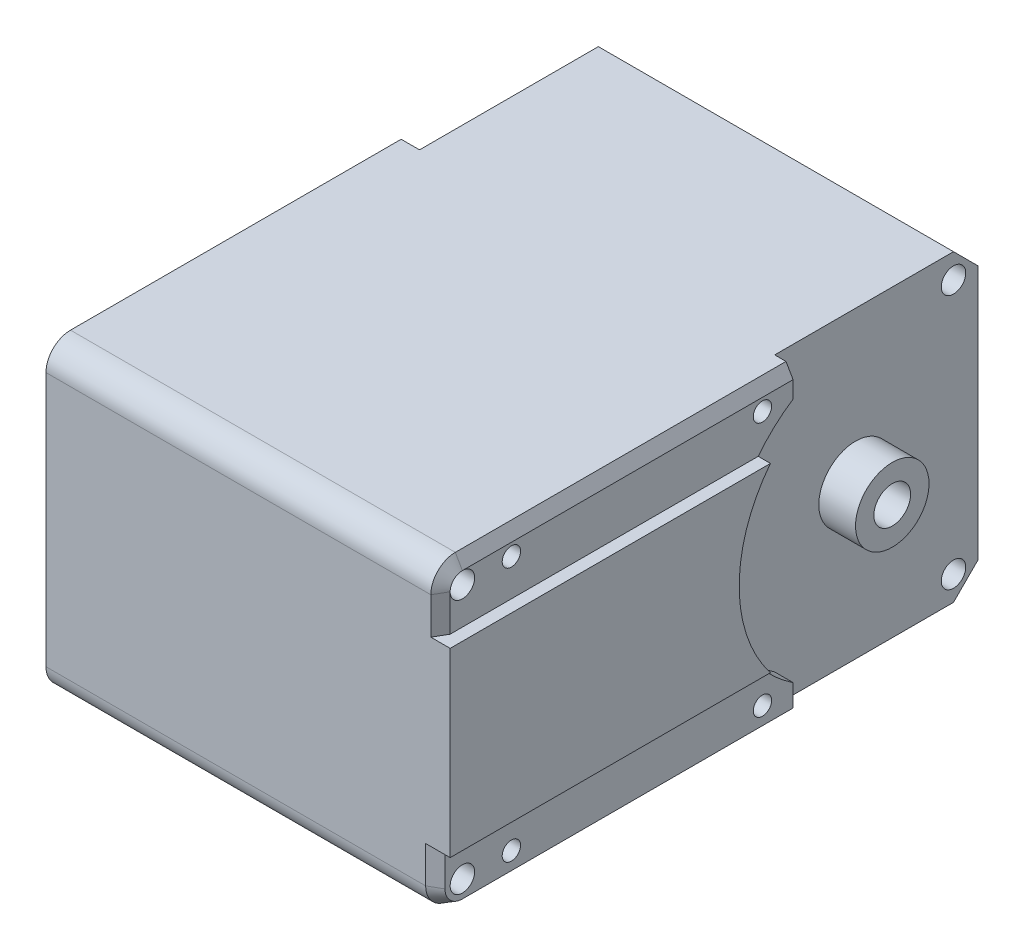
SolidWorks part; units mm, degrees
other "Markup1"
sketch "Sketch5" plane through (27.3, 11.5, -22.8) normal (0.9422, 0.1493, -0.3) x (0.1093, -0.9832, -0.146)
ref_plane "Front Plane" through (0, 0, 0) normal (0, 0, 1) x (1, 0, 0)
ref_plane "Top Plane" through (0, 0, 0) normal (0, 1, 0) x (1, 0, 0)
ref_plane "Right Plane" through (0, 0, 0) normal (1, 0, 0) x (0, 0, -1)
sketch "Sketch3" plane through (0, 0, 0) normal (1, 0, 0) x (0, 0, -1)
  line L1 (-22.8, -12.4) -> (22.8, -12.4)
  line L2 (-22.8, -12.4) -> (-22.8, 12.4)
  line L3 (-22.8, 12.4) -> (22.8, 12.4)
  line L4 (22.8, -12.4) -> (22.8, 12.4)
  line L5 (-22.8, -12.4) -> (22.8, 12.4) construction
  line L6 (-22.8, 12.4) -> (22.8, -12.4) construction
  point P0 (0, 0)
  dimension "D1" = 24.8
  dimension "D2" = 45.6
extrude "Boss-Extrude1" add sketch "Sketch3" along normal blind 29
sketch "Sketch4" plane through (29, 0, 0) normal (1, 0, 0) x (0, 0, -1)
  line L0 (-22.8, -12.4) -> (22.8, -12.4) construction
  line L1 (-22.8, 12.4) -> (6.2, 12.4)
  line L2 (-22.8, 12.4) -> (-22.8, -12.4)
  line L3 (-22.8, -12.4) -> (6.2, -12.4)
  line L4 (6.2, 12.4) -> (6.2, -12.4)
  line L5 (22.8, 0) -> (12.8, 0) construction
  line L6 (22.8, -12.4) -> (22.8, 12.4) construction
  circle A0 centre (12.8, 0) radius 14.5
  dimension "D3" = 29
  dimension "D1" = 29
  dimension "D2" = 10
extrude "Boss-Extrude2" add sketch "Sketch4" along normal blind 1.5 contours L2 L1 L4 L3
sketch "Sketch6" plane through (29, 0, 0) normal (1, 0, 0) x (0, 0, -1)
  line L0 (22.8, 0) -> (12.8, 0) construction
  line L1 (22.8, -12.4) -> (22.8, 12.4) construction
  circle A0 centre (12.8, 0) radius 12
  dimension "D1" = 10
extrude "Cut-Extrude1" cut sketch "Sketch6" along normal up to surface (1.5 mm away) up to face at (30.5, 0, 8.3)
sketch "Sketch7" plane through (30.5, 0, 0) normal (1, 0, 0) x (0, 0, -1)
  line L0 (-22.8, 12.4) -> (-22.8, -12.4) construction
  line L1 (-22.8, 7.4) -> (3.3533, 7.4)
  line L2 (-22.8, 7.4) -> (-22.8, -7.4)
  line L3 (-22.8, -7.4) -> (3.3533, -7.4)
  line L5 (-22.8, -12.4) -> (6.2, -12.4) construction
  line L6 (-22.8, 12.4) -> (6.2, 12.4) construction
  arc A0 (6.2, 10.022) -> (6.2, -10.022) centre (12.8, 0) ccw construction
  arc A1 (3.3533, 7.4) -> (3.3533, -7.4) centre (12.8, 0) ccw
  dimension "D1" = 5
  dimension "D2" = 5
  dimension "D3" = 14.8
extrude "Boss-Extrude3" add sketch "Sketch7" along normal blind 1
sketch "Sketch8" plane through (30.5, 0, 0) normal (1, 0, 0) x (0, 0, -1)
  line L0 (-22.8, -12.4) -> (6.2, -12.4) construction
  line L1 (-22.8, -7.4) -> (-22.8, -12.4) construction
  line L2 (-22.8, 12.4) -> (-22.8, 7.4) construction
  line L3 (-22.8, 12.4) -> (6.2, 12.4) construction
  circle A0 centre (-20.8, 10.4) radius 1
  circle A1 centre (-20.8, -10.4) radius 1
  dimension "D5" = 2
  dimension "D6" = 2
  dimension "D1" = 2
  dimension "D2" = 2
  dimension "D3" = 2
  dimension "D4" = 2
sketch "Sketch9" plane through (0, 0, 0) normal (-1, 0, 0) x (0, 0, 1)
  line L0 (-22.8, -12.4) -> (-22.8, 12.4) construction
  circle A0 centre (-12.8, 0) radius 3
  circle A1 centre (-12.8, 0) radius 1.25
  dimension "D2" = 6
  dimension "D3" = 2.5
  dimension "D1" = 10
ref_plane "Plane1" through (14.5, 0, 0) normal (-1, 0, 0) x (0, 0, 1)
mirror "Mirror2" about plane through (14.5, 0, 0) normal (-1, 0, 0) of "Cut-Extrude1", "Boss-Extrude2"
sketch "Sketch10" plane through (-1.5, 0, 0) normal (-1, 0, 0) x (0, 0, 1)
  line L0 (22.8, 12.4) -> (-6.2, 12.4) construction
  line L1 (5.3, -9.4) -> (17.3, -9.4)
  line L2 (5.3, -9.4) -> (5.3, 9.4)
  line L3 (5.3, 9.4) -> (17.3, 9.4)
  line L4 (17.3, -9.4) -> (17.3, 9.4)
  line L5 (22.8, -12.4) -> (-6.2, -12.4) construction
  line L7 (22.8, 12.4) -> (22.8, -12.4) construction
  dimension "D1" = 3
  dimension "D2" = 3
  dimension "D3" = 18.8
  dimension "D4" = 5.5
  dimension "D5" = 12
extrude "Boss-Extrude5" add sketch "Sketch10" along normal blind 1.5
sketch "Sketch11" plane through (0, -9.4, 0) normal (0, -1, 0) x (1, 0, 0)
  line L3 (-3, 5.3) -> (-3, 17.3) construction
  line L4 (-3, 7.3) -> (-1.5, 5.3)
  line L5 (-1.5, 5.3) -> (-3, 5.3)
  line L6 (-3, 5.3) -> (-3, 7.3)
extrude "Cut-Extrude2" cut sketch "Sketch11" against normal up to surface (18.8 mm away) up to face at (-2.25, 9.4, 11.3)
sketch "Sketch12" plane through (-1.5, 0, 0) normal (-1, 0, 0) x (0, 0, 1)
  line L0 (5.3, 9.4) -> (5.3, -9.4) construction
  line L1 (5.3, -10.4) -> (-0.7, -10.4)
  line L2 (5.3, -10.4) -> (5.3, 9.6)
  line L3 (5.3, 9.6) -> (-0.7, 9.6)
  line L4 (-0.7, -10.4) -> (-0.7, -6.48)
  line L5 (22.8, -12.4) -> (-6.2, -12.4) construction
  line L8 (-2.7, -6.48) -> (-0.7, -6.48)
  line L9 (-2.7, 6.48) -> (-0.7, 6.48)
  line L10 (-0.7, 6.48) -> (-0.7, 9.6)
  arc A0 (-6.2, -10.022) -> (-6.2, 10.022) centre (-12.8, 0) ccw construction
  arc A1 (-6.2, -10.022) -> (-6.2, 10.022) centre (-12.8, 0) ccw construction
  arc A2 (-2.7, -6.48) -> (-2.7, 6.48) centre (-12.8, 0) ccw
  dimension "D1" = 6
  dimension "D2" = 0
  dimension "D3" = 20
  dimension "D4" = 2
  dimension "D5" = 2
extrude "Cut-Extrude3" cut sketch "Sketch12" against normal up to surface (1.5 mm away) up to face at (0, 0, -10.8333)
sketch "Sketch13" plane through (0, 0, 0) normal (-1, 0, 0) x (0, 0, 1)
  line L1 (-0.7, -10.4) -> (5.3, -10.4)
  line L2 (-0.7, -10.4) -> (-0.7, 9.6)
  line L3 (-0.7, 9.6) -> (5.3, 9.6)
  line L4 (5.3, -10.4) -> (5.3, 9.6)
extrude "Cut-Extrude4" cut sketch "Sketch13" against normal blind 5
sketch "Sketch14" plane through (-1.5, 0, 0) normal (-1, 0, 0) x (0, 0, 1)
  line L0 (-22.8, 12.4) -> (-6.2, 12.4) construction
  line L3 (-0.7, 9.6) -> (-0.7, -10.4) construction
  line L4 (22.8, -12.4) -> (-6.2, -12.4) construction
  circle A0 centre (20.8, 10.4) radius 0.75
  circle A1 centre (20.8, -10.4) radius 0.75
  circle A2 centre (-3.7, 10.4) radius 0.75
  circle A3 centre (-3.7, -10.4) radius 0.75
  dimension "D1" = 1.5
  dimension "D2" = 1.5
  dimension "D3" = 1.5
  dimension "D4" = 1.5
  dimension "D5" = 3
  dimension "D6" = 3
  dimension "D7" = 2
  dimension "D8" = 2
extrude "Cut-Extrude5" cut sketch "Sketch14" against normal blind 5
extrude "Cut-Extrude6" cut sketch "Sketch8" against normal blind 5
sketch "Sketch15" plane through (30.5, 0, 0) normal (1, 0, 0) x (0, 0, -1)
  circle A1 centre (3.7, -10.4) radius 0.75
  circle A2 centre (3.7, -10.4) radius 0.75
  circle A3 centre (3.7, 10.4) radius 0.75
  circle A4 centre (3.7, 10.4) radius 0.75
  circle A5 centre (-20.8, -10.4) radius 0.75
  circle A6 centre (-20.8, -10.4) radius 0.75
  circle A7 centre (-20.8, 10.4) radius 0.75
  circle A8 centre (-20.8, 10.4) radius 0.75
  dimension "D1" = 0
  dimension "D2" = 0
  dimension "D3" = 0
  dimension "D4" = 0
sketch "Sketch16" plane through (30.5, 0, 0) normal (1, 0, 0) x (0, 0, -1)
extrude "Cut-Extrude7" cut sketch "Sketch15" against normal blind 5 contours A4 | A2
sketch "Sketch17" plane through (30.5, 0, 0) normal (1, 0, 0) x (0, 0, -1)
  line L0 (-20.8, -10.4) -> (-16.8, -10.4) construction
  line L1 (-20.8, 10.4) -> (-16.8, 10.4) construction
  circle A3 centre (-16.8, 10.4) radius 0.75
  circle A4 centre (-16.8, -10.4) radius 0.75
  dimension "D3" = 1.5
  dimension "D4" = 1.5
  dimension "D1" = 4
  dimension "D2" = 4
extrude "Cut-Extrude8" cut sketch "Sketch17" against normal blind 5
mirror "Mirror3" about plane through (0, 0, 0) normal (0, 0, 1) of "Cut-Extrude6"
sketch "Sketch18" plane through (29, 0, 0) normal (1, 0, 0) x (0, 0, -1)
  circle A0 centre (12.8, 0) radius 3
  dimension "D1" = 6
extrude "Boss-Extrude6" add sketch "Sketch18" along normal blind 3
sketch "Sketch19" plane through (32, 0, 0) normal (1, 0, 0) x (0, 0, -1)
  circle A0 centre (12.8, 0) radius 1.5
  dimension "D1" = 3
extrude "Cut-Extrude9" cut sketch "Sketch19" against normal up to surface (3 mm away) up to face at (29, 0, -9.8)
fillet "Fillet1" radius 2 2 edges at (14.5, -12.4, 22.8) (14.5, 12.4, 22.8)
chamfer "Chamfer1" distance 2 angle 45 2 edges at (14.5, -12.4, -22.8) (14.5, 12.4, -22.8)
chamfer "Chamfer2" distance 1 angle 30 6 edges at (30.5, -8.9, 22.8) (30.5, -11.8142, 22.2142) (30.5, -12.4, 7.3) (30.5, 8.9, 22.8) (30.5, 11.8142, 22.2142) (30.5, 12.4, 7.3)
extrude "Boss-Extrude7" add sketch "Sketch9" along normal blind 3
